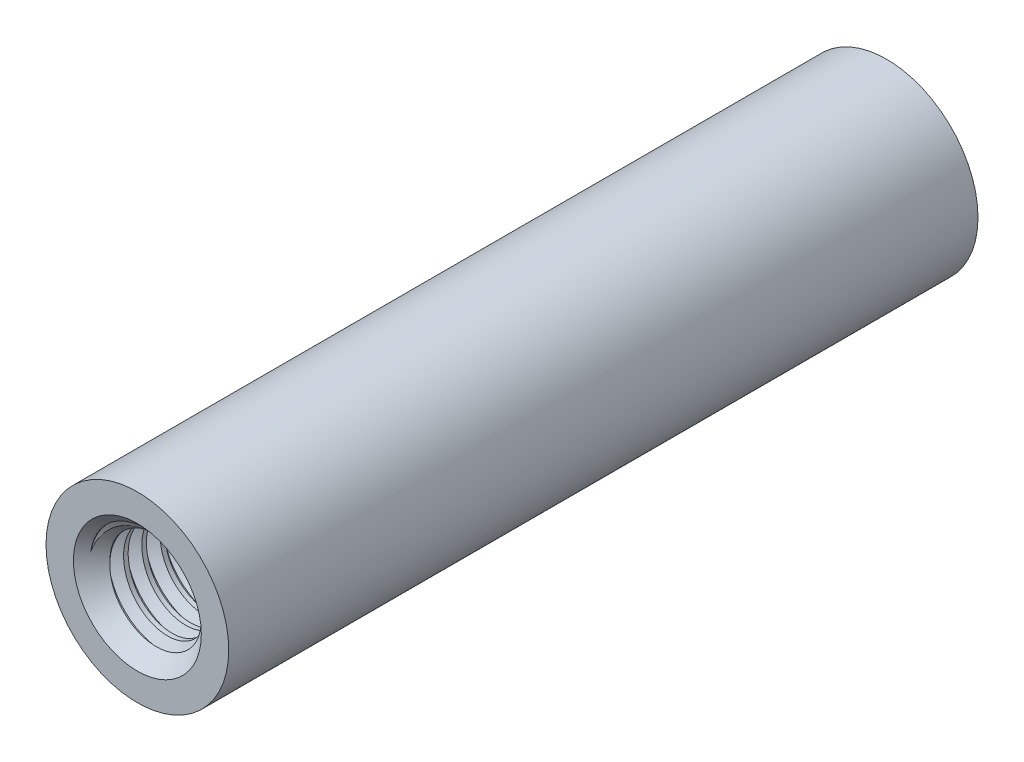
SolidWorks part; units mm, degrees
ref_plane "Front Plane" through (0, 0, 0) normal (0, 0, 1) x (1, 0, 0)
ref_plane "Top Plane" through (0, 0, 0) normal (0, 1, 0) x (1, 0, 0)
ref_plane "Right Plane" through (0, 0, 0) normal (1, 0, 0) x (0, 0, -1)
sketch "Sketch1" plane through (0, 0, 0) normal (0, 1, 0) x (1, 0, 0)
  line L0 (0, -292.8551) -> (0, 6.5) construction
  line L2 (2.5, 8.5) -> (2.5, 20.5)
  line L3 (2.5, 20.5) -> (5, 20.5)
  line L4 (5, 20.5) -> (5, 0)
  line L5 (5, 0) -> (0, 0)
  line L6 (0, 0) -> (0, 6.5)
  line L7 (-292.8551, 0) -> (14349.8979, 0) construction
  line L8 (2.5, 8.5) -> (0, 6.5)
  dimension "D1" = 41
  dimension "D2" = 10
  dimension "D3" = 5
  dimension "D4" = 12
  dimension "D5" = 2
revolve "Revolve1" add sketch "Sketch1" angle 360 about L0
chamfer "Chamfer2" distance 1 angle 45 1 edges at (2.5, 0, -20.5)
thread "Thread2" pitch 1 method cut profile "Thread Profile2" start angle 0, offset 2, length 0, pitch 1, diameter 5
ref_plane "Plane2" through (2.5, 0, -21.5) normal (0, -1, 0) x (1, 0, 0)
sketch "Thread Profile2" plane through (2.5, 0, -21.5) normal (0, -1, 0) x (1, 0, 0)
  line L0 (0, 0) -> (0, 1) construction
  line L1 (0, 0) -> (0.5413, 0.3125)
  line L2 (0.5413, 0.3125) -> (0.5413, 0.4375)
  line L3 (0.5413, 0.4375) -> (0, 0.75)
  line L4 (0.5413, 0.375) -> (0, 0.375) construction
  line L11 (0, 0) -> (0, 0.75)
  point P2 (0, 0)
  dimension "Pitch" = 1
  dimension "Profile_Angle" = 60
  dimension "Profile_Land" = 0.125
  dimension "Profile_Height" = 0.5413
mirror "Mirror2" about plane through (5, 0, 0) normal (0, 0, 1) of "Chamfer2", "Revolve1"
thread "Thread3" pitch 1 method cut profile "Thread Profile3" start angle 0, offset 2, length 0, pitch 1, diameter 5
ref_plane "Plane3" through (-2.5, 0, 21.5) normal (0, -1, 0) x (-1, 0, 0)
sketch "Thread Profile3" plane through (-2.5, 0, 21.5) normal (0, -1, 0) x (-1, 0, 0)
  line L0 (0, 0) -> (0, 1) construction
  line L1 (0, 0) -> (0.5413, 0.3125)
  line L2 (0.5413, 0.3125) -> (0.5413, 0.4375)
  line L3 (0.5413, 0.4375) -> (0, 0.75)
  line L4 (0.5413, 0.375) -> (0, 0.375) construction
  line L11 (0, 0) -> (0, 0.75)
  point P2 (0, 0)
  dimension "Pitch" = 1
  dimension "Profile_Angle" = 60
  dimension "Profile_Land" = 0.125
  dimension "Profile_Height" = 0.5413
